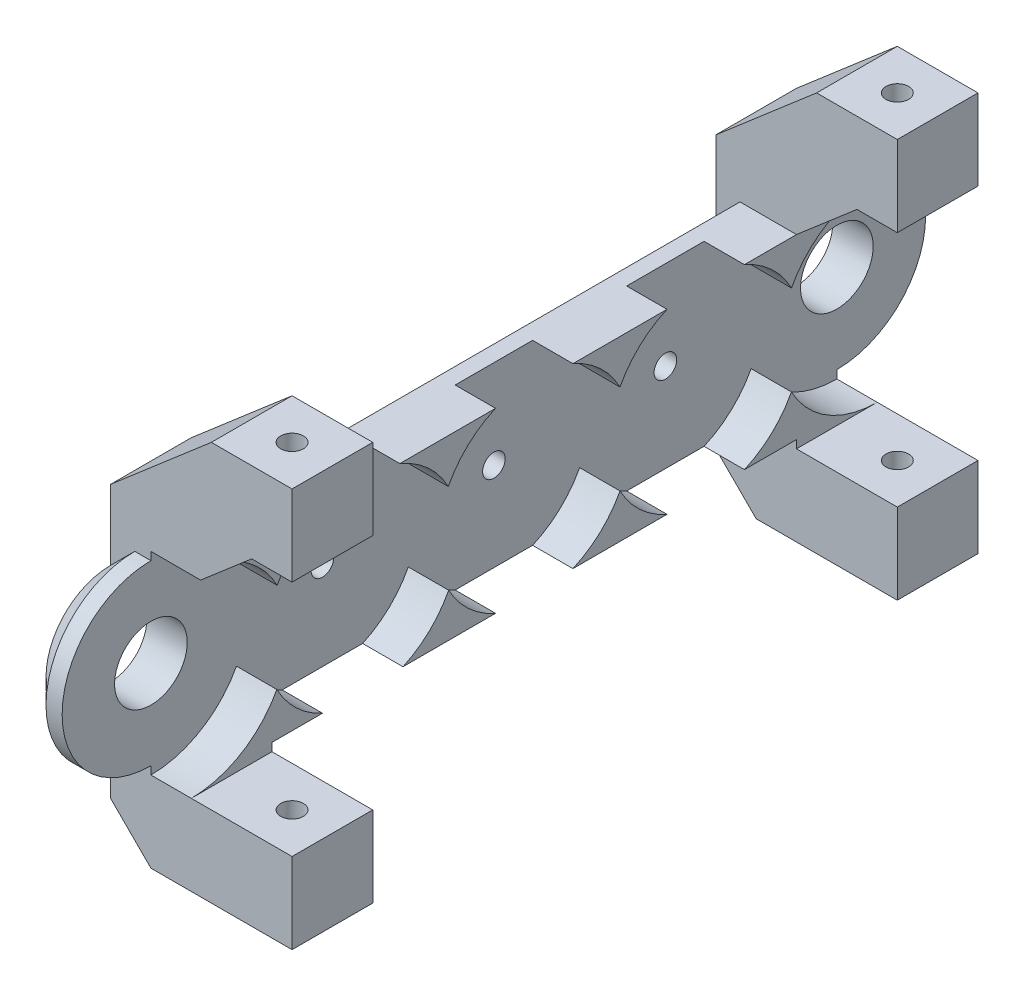
SolidWorks part; units mm, degrees
ref_plane "Front Plane" through (0, 0, 0) normal (0, 0, 1) x (1, 0, 0)
ref_plane "Top Plane" through (0, 0, 0) normal (0, 1, 0) x (1, 0, 0)
ref_plane "Right Plane" through (0, 0, 0) normal (1, 0, 0) x (0, 0, -1)
sketch "Sketch1" plane through (0, 0, 0) normal (1, 0, 0) x (0, 0, -1)
  line L0 (0, 0) -> (89.5, 0) construction
  line L1 (0, 11) -> (85, 11)
  line L2 (0, -11) -> (85, -11)
  line L3 (85, 11) -> (85, 0) construction
  line L4 (85, 0) -> (85, -11) construction
  line L5 (42.5, 11) -> (42.5, -11) construction
  line L6 (165.5, 0) -> (170, 0) construction
  circle A0 centre (0, 0) radius 4.5
  arc A1 (0, 11) -> (0, -11) centre (0, 0) ccw
  arc A2 (85, 11) -> (85, -11) centre (85, 0) cw
  circle A3 centre (0, 0) radius 35 construction
  circle A4 centre (85, 0) radius 35 construction
  circle A6 centre (85, 0) radius 4.5
  point P3 (85, 0)
  dimension "D1" = 85
  dimension "D3" = 70
  dimension "D2" = 85
extrude "Boss-Extrude1" add sketch "Sketch1" along normal blind 10 contours A0 | A6 | L1 A2 L2 A1 region at (0, 0, 0) region at (0, 0, -85)
sketch "Sketch3" plane through (0, 0, 0) normal (-1, 0, 0) x (0, 0, 1)
  line L0 (-63.75, 0) -> (-42.5, 0) construction
  line L1 (-42.5, 0) -> (-21.25, 0) construction
  line L2 (-85, 0) -> (-63.75, 0) construction
  line L3 (-21.25, 0) -> (0, 0) construction
  line L4 (-170, 0) -> (-148.75, 0) construction
  line L5 (-148.75, 0) -> (-127.5, 0) construction
  line L6 (-127.5, 0) -> (-106.25, 0) construction
  line L7 (-106.25, 0) -> (-85, 0) construction
  circle A2 centre (-42.5, 0) radius 1.4
  circle A3 centre (-63.75, 0) radius 1.4
  circle A4 centre (-21.25, 0) radius 1.4
  circle A5 centre (-148.75, 0) radius 1.4
  circle A6 centre (-127.5, 0) radius 1.4
  circle A7 centre (-106.25, 0) radius 1.4
  dimension "D1" = 2.8
extrude "Cut-Extrude1" cut sketch "Sketch3" against normal through all
sketch "Sketch6" plane through (10, 0, 0) normal (1, 0, 0) x (0, 0, -1)
  circle A0 centre (0, 0) radius 12
  circle A3 centre (85, 0) radius 12
  circle A5 centre (63.75, 0) radius 12
  circle A6 centre (42.5, 0) radius 12
  circle A7 centre (21.25, -0.085) radius 12
  line M4 (85, 11) -> (0, 11)
  circle M7 centre (0, 0) radius 4.5
  line M14 (0, -11) -> (85, -11)
  circle M20 centre (21.25, 0) radius 1.4
  circle M22 centre (42.5, 0) radius 1.4
  circle M23 centre (63.75, 0) radius 1.4
  circle M24 centre (85, 0) radius 4.5
  arc M26 (0, 11) -> (0, -11) centre (0, 0) ccw
  arc M41 (85, -11) -> (85, 11) centre (85, 0) ccw
  dimension "D1" = 24
sketch "Sketch7" plane through (0, 0, 0) normal (0, 0, 1) x (1, 0, 0)
  line L1 (0, 11) -> (0, 16.6971)
  line L3 (0, 11) -> (10, 11)
  line L4 (22.4897, 27.4454) -> (12.4897, 27.4454)
  line L5 (5.2275, 15.015) -> (5.4467, 43.2136) construction
  line L6 (22.4897, 17.4454) -> (17.4897, 17.4454)
  line L7 (12.4897, 27.4454) -> (0, 16.6971)
  line L8 (17.4897, 17.4454) -> (10, 11)
  line L9 (22.4897, 17.4454) -> (22.4897, 27.4454)
  dimension "D1" = 10
  dimension "D2" = 10
extrude "Boss-Extrude2" add sketch "Sketch7" against normal blind 10 separate body
ref_point "Point1"
ref_point "Point2"
ref_axis "Axis1" through (10, 0, -42.5) along (-1, 0, 0)
ref_plane "Plane1" through (0, 0, -42.5) normal (0, 0, -1) x (-1, 0, 0)
pattern_linear "LPattern1" count 2 spacing 75 along (0, 0, -1) of "Boss-Extrude2"
sketch "Sketch8" plane through (0, -11, 0) normal (0, -1, 0) x (-1, 0, 0)
  line L0 (-10, 0) -> (0, 0)
  line L1 (0, 0) -> (0, 10)
  line L2 (0, 10) -> (-10, 10)
  line L3 (-10, 10) -> (-10, 0)
extrude "Boss-Extrude3" add sketch "Sketch8" along normal blind 1
sketch "Sketch10" plane through (10, 0, 0) normal (1, 0, 0) x (0, 0, -1)
  line L0 (10, -12) -> (10, -22)
  line L1 (10, -22) -> (0, -22)
  line L2 (0, -22) -> (0, -12)
  line L3 (0, -12) -> (10, -12)
extrude "Boss-Extrude5" add sketch "Sketch10" along normal up to surface (12.4897 mm away) and the other way blind 10 up to face at (22.4897, 22.4454, -5)
chamfer "Chamfer3" distance 5 angle 45 1 edges at (0, -22, -5)
sketch "Sketch14" plane through (0, 0, 0) normal (-1, 0, 0) x (0, 0, 1)
  line L1 (-184.9305, -31.2602) -> (14.9305, -31.2602)
  line L2 (-184.9305, -31.2602) -> (-184.9305, 31.2602)
  line L3 (-184.9305, 31.2602) -> (14.9305, 31.2602)
  line L4 (14.9305, -31.2602) -> (14.9305, 31.2602)
  line L5 (-184.9305, -31.2602) -> (14.9305, 31.2602) construction
  line L6 (-184.9305, 31.2602) -> (14.9305, -31.2602) construction
  point P0 (-85, 0)
pattern_linear "LPattern3" count 2 spacing 75 along (0, 0, -1) of "Boss-Extrude3", "Boss-Extrude5", "Chamfer3"
combine bodies "Combine1" operation type add bodies to combine 106 127 108
extrude "Cut-Extrude3" cut sketch "Sketch6" against normal blind 5 and the other way blind 10 contours A7 A0 M4 M26 M14 M7 | A6 A7 A0 M4 M14 M20 | A0 A7 | A7 A6 A5 M14 M4 M22 | A6 A7 | A6 A5 A3 M14 M4 M23 | A5 A6 | A3 A5 | A5 A3 M14 M41 M4 M24 | A0 M4 M14 M26 | A3 M14 M4 M41 region at (10, -0.0425, -10.625) region at (10, 2.9216, -11.9543) region at (10, -0.0358, -8.9415) region at (10, 11.2929, -2.3979) region at (10, -0.0425, -31.875) region at (10, 8.5462, -34.5181) region at (10, 0, -53.125) region at (10, 8.5623, -55.7851) region at (10, 0, -74.375) region at (10, 8.5604, -77.0369) region at (10, 9.7936, -91.4141)
sketch "Sketch15" plane through (0, 27.4454, 0) normal (0, 1, 0) x (1, 0, 0)
  line L0 (17.4897, 85) -> (17.4897, 75) construction
  line L1 (22.4897, 85) -> (12.4897, 85) construction
  line L2 (17.4897, 10) -> (17.4897, 0) construction
  line L3 (22.4897, 10) -> (12.4897, 10) construction
  circle A0 centre (17.4897, 80) radius 1.4
  circle A1 centre (17.4897, 5) radius 1.4
extrude "Cut-Extrude4" cut sketch "Sketch15" against normal blind 70
chamfer "Chamfer4" distance 3 angle 45 4 edges at (0, -11, -42.5) (0, 11, -42.5) (0, 0, -96) (0, 0, 11)
